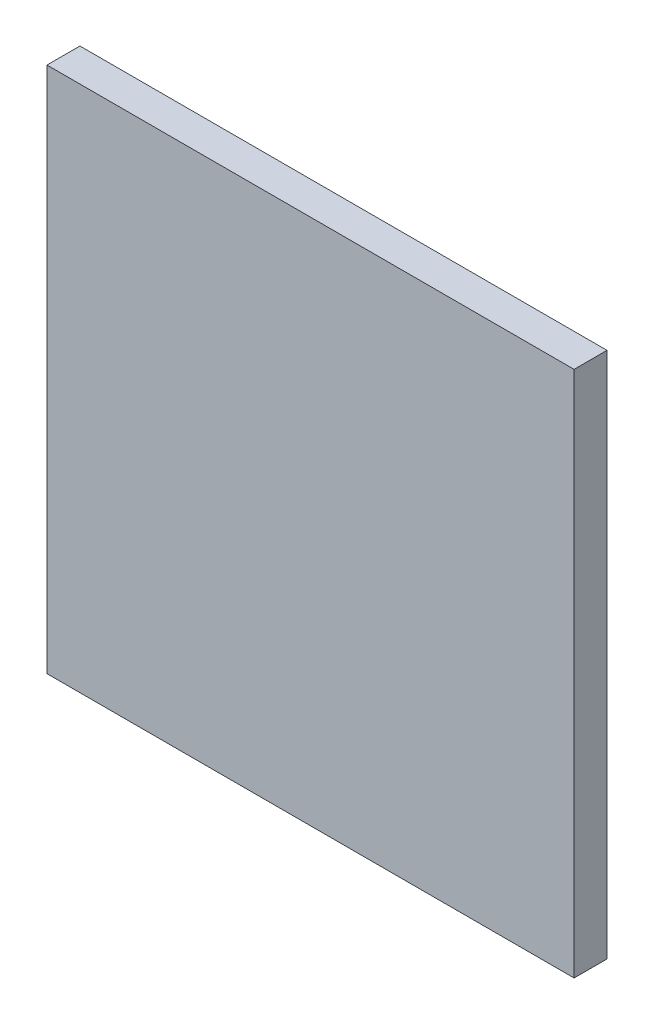
SolidWorks part; units mm, degrees
ref_plane "Front Plane" through (0, 0, 0) normal (0, 0, 1) x (1, 0, 0)
ref_plane "Top Plane" through (0, 0, 0) normal (0, 1, 0) x (1, 0, 0)
ref_plane "Right Plane" through (0, 0, 0) normal (1, 0, 0) x (0, 0, -1)
sketch "Sketch1" plane through (0, 0, 0) normal (0, 0, 1) x (1, 0, 0)
  line L1 (0, 0) -> (50.8, 0)
  line L2 (0, 0) -> (0, 50.8)
  line L3 (0, 50.8) -> (50.8, 50.8)
  line L4 (50.8, 0) -> (50.8, 50.8)
  dimension "D1" = 50.8
  dimension "D2" = 50.8
extrude "Boss-Extrude1" add sketch "Sketch1" along normal blind 3.175
